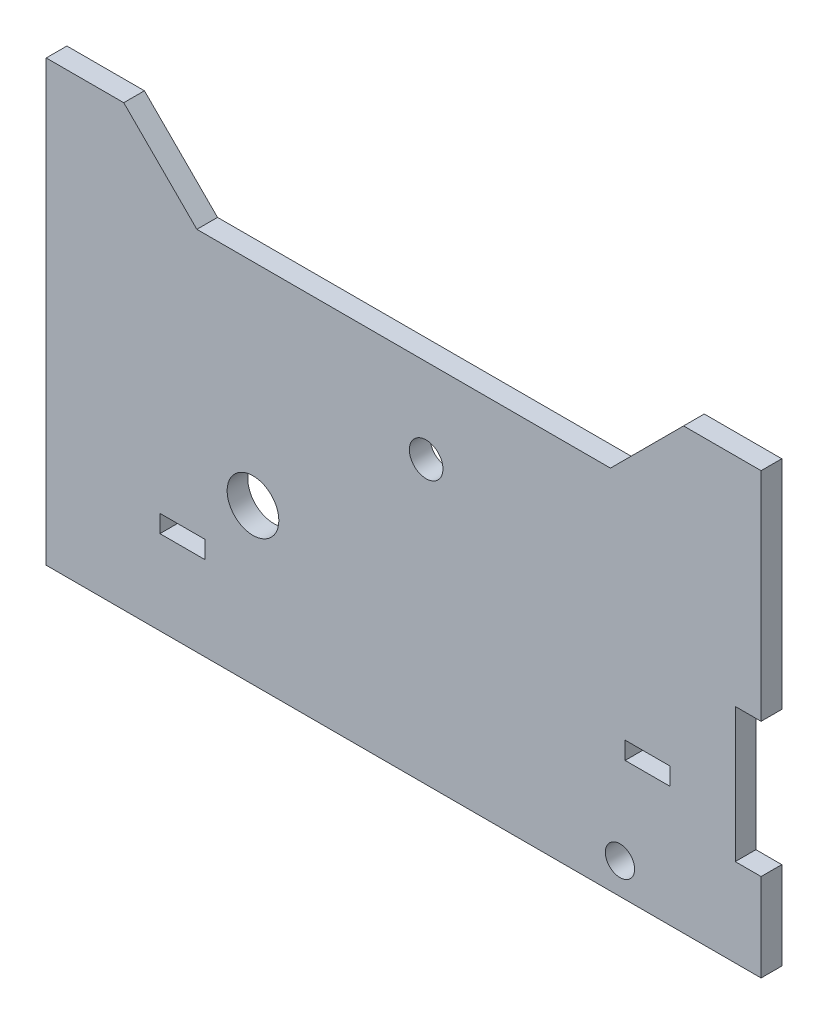
SolidWorks part; units mm, degrees
ref_plane "Front Plane" through (0, 0, 0) normal (0, 0, 1) x (1, 0, 0)
ref_plane "Top Plane" through (0, 0, 0) normal (0, 1, 0) x (1, 0, 0)
ref_plane "Right Plane" through (0, 0, 0) normal (1, 0, 0) x (0, 0, -1)
sketch "Sketch1" plane through (0, 0, 0) normal (0, 0, 1) x (1, 0, 0)
  line L2 (-86, -30) -> (-86, 30)
  line L6 (52.3, 13) -> (47.3, 13)
  line L7 (47.3, 13) -> (47.3, -13)
  line L8 (47.3, -13) -> (52.3, -13)
  line L11 (52.3, 30) -> (52.3, 13)
  line L12 (52.3, -13) -> (52.3, -30)
  line L23 (52.3, 30) -> (-86, 30)
  line L24 (26, -3.3) -> (34.7, -3.3)
  line L25 (26, -3.3) -> (26, -6.7)
  line L26 (26, -6.7) -> (34.7, -6.7)
  line L27 (34.7, -3.3) -> (34.7, -6.7)
  line L28 (26, -5) -> (34.7, -5) construction
  line L29 (30.35, -3.3) -> (30.35, -6.7) construction
  line L30 (-86, -30) -> (52.3, -30)
  line L31 (-55.3, -12) -> (-64, -12) construction
  line L32 (-64, -10.3) -> (-55.3, -10.3)
  line L33 (-64, -10.3) -> (-64, -13.7)
  line L34 (-64, -13.7) -> (-55.3, -13.7)
  line L35 (-55.3, -10.3) -> (-55.3, -13.7)
  line L36 (-52.65, -10.3) -> (-52.65, -13.7) construction
  circle A3 centre (-46, 0) radius 5
  circle A4 centre (25, -24) radius 2.83
  circle A5 centre (-12.5, 24.5) radius 3.25
  point P1 (-12, 0)
  dimension "D5" = 10
  dimension "D17" = 5.66
  dimension "D25" = 6.5
  dimension "D1" = 40
  dimension "D8" = 26
  dimension "D13" = 8.7
  dimension "D14" = 3.4
  dimension "D18" = 111
  dimension "D27" = 33.5
  dimension "D28" = 24.5
  dimension "D6" = 5
  dimension "D4" = 24
  dimension "D7" = 116.35
  dimension "D9" = 60
  dimension "D3" = 138.3
  dimension "D10" = 5
  dimension "D11" = 12
  dimension "D12" = 33.35
extrude "Boss-Extrude1" add sketch "Sketch1" along normal mid plane 4
sketch "Sketch2" plane through (0, 0, 0) normal (0, 0, 1) x (1, 0, 0)
  line L0 (-86, 30) -> (52.3, 30)
  line L1 (52.3, 30) -> (52.3, 55)
  line L2 (52.3, 55) -> (37.3, 55)
  line L3 (37.3, 55) -> (23.1579, 40.8579)
  line L4 (23.1579, 40.8579) -> (-56.8579, 40.8579)
  line L5 (-56.8579, 40.8579) -> (-71, 55)
  line L6 (-71, 55) -> (-86, 55)
  line L7 (-86, 55) -> (-86, 30)
  point P9 (0, 0)
  point P12 (0, 0)
  dimension "D1" = 25
  dimension "D2" = 15
  dimension "D3" = 20
  dimension "D4" = 135
extrude "Boss-Extrude2" add sketch "Sketch2" along normal mid plane 4
sketch "Sketch3" plane through (0, 0, 2) normal (0, 0, 1) x (1, 0, 0)
  line L0 (26, -5) -> (34.7, -5) construction
  line L1 (26, -3.3) -> (26, -6.7) construction
  line L2 (34.7, -6.7) -> (34.7, -3.3) construction
  line L3 (30.35, -3.3) -> (30.35, -6.7) construction
  line L4 (34.7, -3.3) -> (26, -3.3) construction
  line L5 (26, -6.7) -> (34.7, -6.7) construction
  line L6 (-64, -12) -> (-55.3, -12) construction
  line L7 (-64, -10.3) -> (-64, -13.7) construction
  line L8 (-55.3, -13.7) -> (-55.3, -10.3) construction
  line L9 (-59.65, -10.3) -> (-59.65, -13.7) construction
  line L10 (-55.3, -10.3) -> (-64, -10.3) construction
  line L11 (-64, -13.7) -> (-55.3, -13.7) construction
sketch "Sketch4" plane through (47.3, 0, 0) normal (1, 0, 0) x (0, 0, -1)
  line L0 (-2, 0) -> (2, 0) construction
  line L1 (-2, -13) -> (-2, 13) construction
  line L2 (2, -13) -> (2, 13) construction
equation "\"back_boost\"= 7"
equation "\"D18@Sketch1\"=\"back_boost\"+104.00mm"
equation "\"D1@Sketch1\"=33.00mm+\"back_boost\""
equation "\"D7@Sketch1\"=109.35mm+\"back_boost\""
equation "\"D3@Sketch1\"=131.30mm+\"back_boost\""
equation "\"D12@Sketch1\"=\"back_boost\"+26.35mm"
